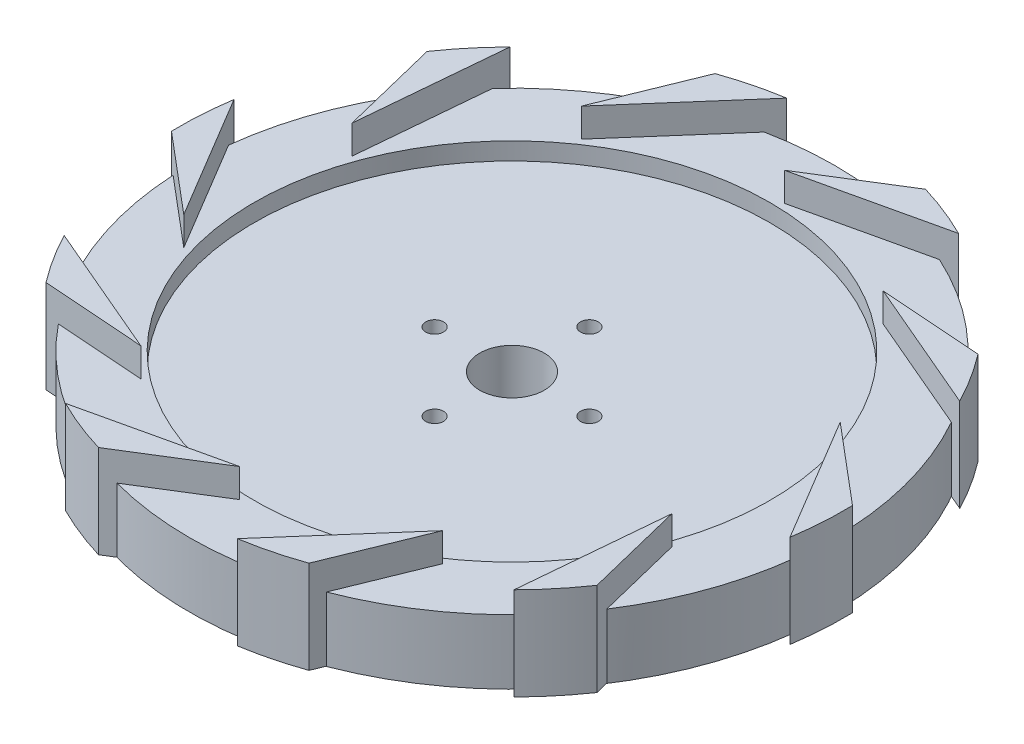
SolidWorks part; units mm, degrees
ref_plane "Front Plane" through (0, 0, 0) normal (0, 0, 1) x (1, 0, 0)
ref_plane "Top Plane" through (0, 0, 0) normal (0, 1, 0) x (1, 0, 0)
ref_plane "Right Plane" through (0, 0, 0) normal (1, 0, 0) x (0, 0, -1)
sketch "Sketch3" plane through (0, 0, 0) normal (0, 0, 1) x (1, 0, 0)
  line L0 (0, 0) -> (0, 40.1505) construction
  line L1 (-63.5, 16.0734) -> (-50.8, 16.0734)
  line L2 (-50.8, 16.0734) -> (-50.8, 12.6339)
  line L3 (-50.8, 12.6339) -> (0, 12.6339)
  line L4 (0, 12.6339) -> (0, 3.3734)
  line L5 (0, 3.3734) -> (-63.5, 3.3734)
  line L6 (-63.5, 3.3734) -> (-63.5, 16.0734)
  dimension "D1" = 12.7
  dimension "D2" = 63.5
  dimension "D3" = 50.8
revolve "Body" add sketch "Sketch3" angle 360 about L0
sketch "Sketch4" plane through (0, 0, 0) normal (0, 1, 0) x (1, 0, 0)
  line L0 (1.5533, 52.0769) -> (18.687, 62.7276)
  line L2 (29.4601, 58.4471) -> (1.5533, 52.0769)
  arc A0 (18.687, 62.7276) -> (29.4601, 58.4471) centre (0, 0) cw
extrude "Guide Vanes" add sketch "Sketch4" along direction (0, 1, 0) on the side of the normal blind 15.748 and the other way blind 2.54 from offset 5.969
pattern_circular "CirPattern4" count 10 over 360 about axis through (0, 16.0734, 0) along (0, -1, 0) of "Guide Vanes"
sketch "Sketch5" plane through (0, 3.3734, 0) normal (0, -1, 0) x (1, 0, 0)
  circle A0 centre (0, 0) radius 60.325
  dimension "D1" = 120.65
sketch "Sketch6" plane through (0, 12.6339, 0) normal (0, 1, 0) x (1, 0, 0)
  circle A0 centre (0, 0) radius 6.35
  dimension "D1" = 12.7
extrude "Cut-Extrude1" cut sketch "Sketch6" against normal through all
sketch "Sketch7" plane through (0, 12.6339, 0) normal (0, 1, 0) x (1, 0, 0)
  circle A0 centre (0, 15.24) radius 1.7526
  circle A1 centre (0, 0) radius 6.35 construction
  dimension "D1" = 3.5052
  dimension "D2" = 15.24
extrude "Cut-Extrude2" cut sketch "Sketch7" against normal through all
pattern_circular "CirPattern5" count 4 over 360 about axis through (0, 12.6339, 0) along (0, 1, 0) of "Cut-Extrude2"
